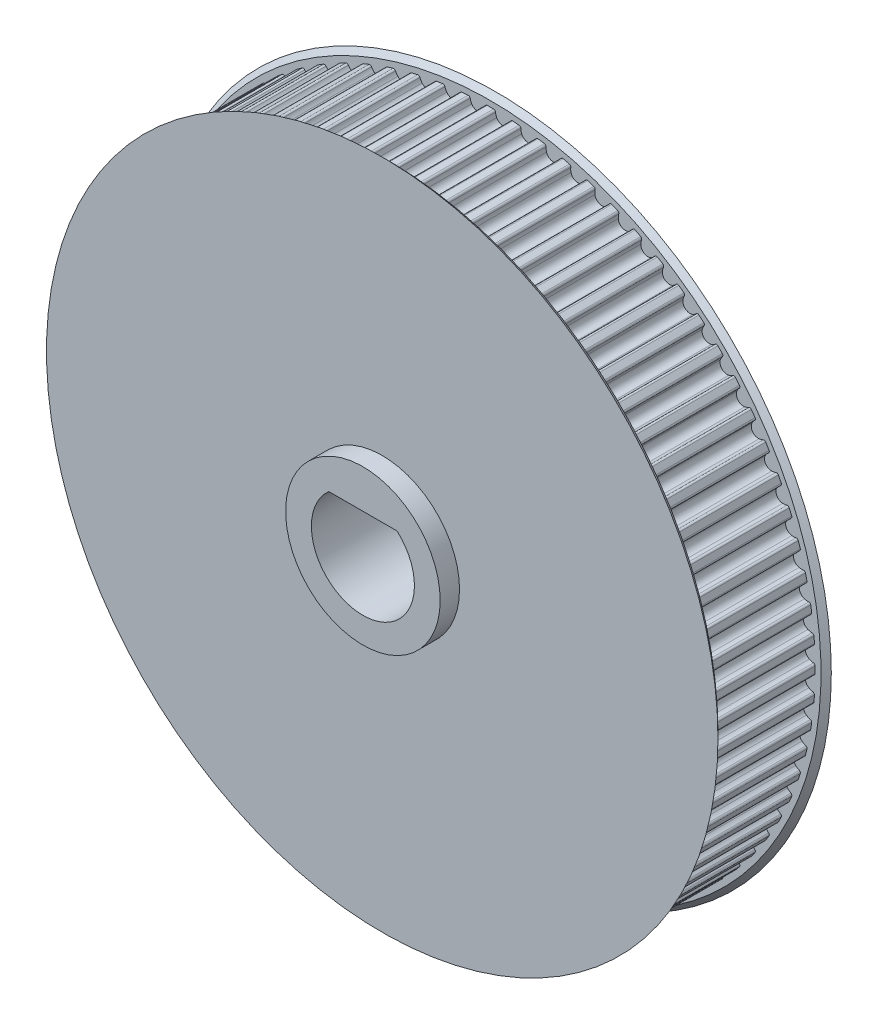
SolidWorks part; units mm, degrees
ref_plane "Front Plane" through (0, 0, 0) normal (0, 0, 1) x (1, 0, 0)
ref_plane "Top Plane" through (0, 0, 0) normal (0, 1, 0) x (1, 0, 0)
ref_plane "Right Plane" through (0, 0, 0) normal (1, 0, 0) x (0, 0, -1)
sketch "Sketch1" plane through (0, 0, 0) normal (0, 0, 1) x (1, 0, 0)
  circle A0 centre (0, 0) radius 25.4648
  dimension "D1" = 50.9296
extrude "Boss-Extrude1" add sketch "Sketch1" along normal mid plane 8
sketch "Sketch3" plane through (0, 0, 4) normal (0, 0, 1) x (1, 0, 0)
  line L0 (0, 0) -> (0, 25.4648) construction
  line L1 (0, 0) -> (0.9605, 24.4459) construction
  line L2 (0, 25.4648) -> (0, 25.2148)
  line L3 (1.3993, 25.4263) -> (1.3881, 25.1895) construction
  line L4 (0.9997, 25.4452) -> (1.3993, 25.4263)
  line L5 (0.9605, 24.4459) -> (0.9997, 25.4452) construction
  line L6 (1.9979, 25.3863) -> (1.9783, 25.1371)
  circle A0 centre (0, 0) radius 25.4648 construction
  arc A1 (0, 25.2148) -> (0.2465, 25.2136) centre (0, 0) cw
  circle A2 centre (0, 0) radius 25.4648
  circle A3 centre (0, 0) radius 25.4648
  arc A4 (0.2465, 25.2136) -> (0.3941, 25.08) centre (0.245, 25.0636) cw
  arc A5 (0.3941, 25.08) -> (0.4858, 24.7584) centre (1.3881, 25.1895) ccw
  arc A6 (0.4858, 24.7584) -> (1.4582, 24.7202) centre (0.9821, 24.9955) ccw
  arc A7 (1.9783, 25.1371) -> (1.7325, 25.1552) centre (0, 0) ccw
  arc A8 (1.7325, 25.1552) -> (1.5748, 25.0336) centre (1.7222, 25.0056) ccw
  arc A9 (1.5748, 25.0336) -> (1.4582, 24.7202) centre (0.5925, 25.2207) cw
  dimension "D4" = 0.15
  dimension "D5" = 1
  dimension "D7" = 0.55
  dimension "D1" = 2.25
  dimension "D3" = 0.25
  dimension "D6" = 0.4
  dimension "D8" = 1
  dimension "D2" = 0
extrude "Cut-Extrude1" cut sketch "Sketch3" against normal up to surface (8 mm away) contours A9 A8 A7 L6 L5 L4 L2 A1 A4 A5 A6 | L5 L4
pattern_circular "CirPattern1" count 80 over 360 about axis through (0, 0, 0) along (0, 0, 1) of "Cut-Extrude1"
sketch "Sketch4" plane through (0, 0, 4) normal (0, 0, 1) x (1, 0, 0)
  circle A0 centre (0, 0) radius 26.0648
  dimension "D1" = 52.1296
extrude "Boss-Extrude2" add sketch "Sketch4" along normal blind 0.4
mirror "Mirror1" about plane through (0, 0, 0) normal (0, 0, 1) of "Boss-Extrude2"
chamfer "Chamfer1" distance 0.4 angle 45 2 edges at (26.0648, 0, -4) (26.0648, 0, 4)
sketch "Sketch5" plane through (0, 0, 4.4) normal (0, 0, 1) x (1, 0, 0)
  circle A0 centre (0, 0) radius 4
  dimension "D1" = 8
extrude "Cut-Extrude2" cut sketch "Sketch5" against normal through all
sketch "Sketch7" plane through (0, 0, 4.4) normal (0, 0, 1) x (1, 0, 0)
  circle A0 centre (0, 0) radius 6
  circle A1 centre (0, 0) radius 4 construction
  circle A2 centre (0, 0) radius 4
  dimension "D1" = 12
extrude "Boss-Extrude3" add sketch "Sketch7" along normal blind 1.5
sketch "Sketch8" plane through (0, 0, 5.9) normal (0, 0, 1) x (1, 0, 0)
  line L0 (-2.6458, 3) -> (2.6458, 3)
  circle A0 centre (0, 0) radius 4 construction
  arc A1 (-2.6458, 3) -> (2.6458, 3) centre (0, 0) cw
  circle M3 centre (0, 0) radius 4
  dimension "D1" = 3
extrude "Boss-Extrude4" add sketch "Sketch8" against normal up to surface (10.3 mm away) contours L0 M3
equation "\"n\"= 80'teeth number"
equation "\"p\"= 2mm'tooth spacing"
equation "\"pd\"= \"n\" * \"p\" / pi"
equation "\"D1@Sketch1\"=\"pd\""
equation "\"halfToothAngle\"= 180 / \"n\""
equation "\"D1@Sketch3\"=\"halfToothAngle\""
equation "\"D1@CirPattern1\"=\"n\""
equation "\"flangeDia\"= \"pd\" + 1.2"
equation "\"D1@Sketch4\"=\"flangeDia\""
